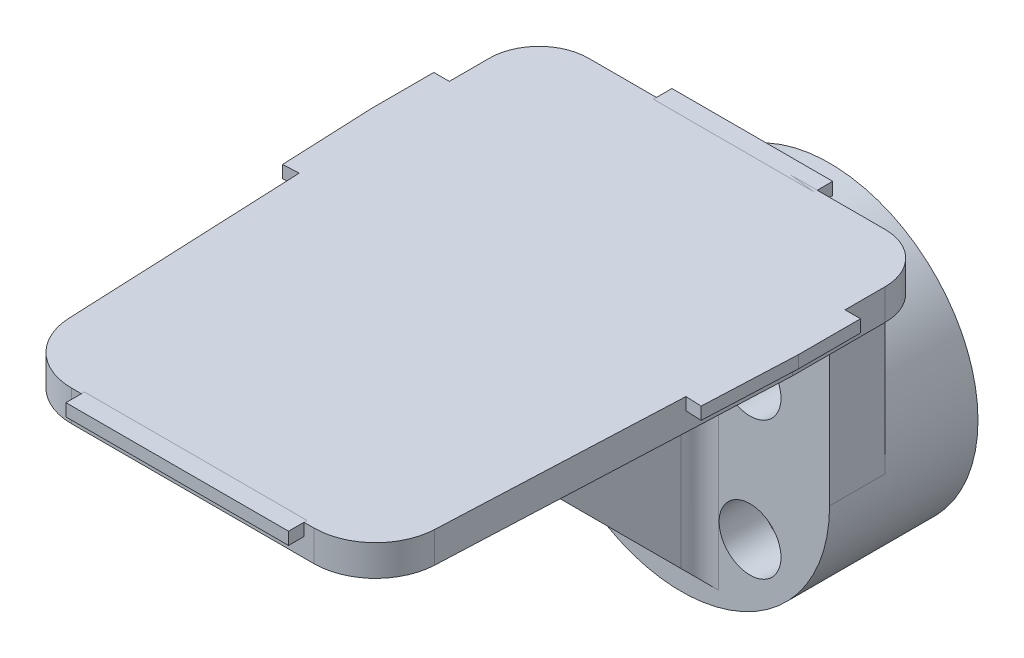
SolidWorks part; units mm, degrees
ref_plane "Front Plane" through (0, 0, 0) normal (0, 0, 1) x (1, 0, 0)
ref_plane "Top Plane" through (0, 0, 0) normal (0, 1, 0) x (1, 0, 0)
ref_plane "Right Plane" through (0, 0, 0) normal (1, 0, 0) x (0, 0, -1)
sketch "Sketch1" plane through (0, 0, 0) normal (0, 0, 1) x (1, 0, 0)
  line L0 (0, 0) -> (0, 50000) construction
  line L1 (0.349, 0) -> (50000.349, 0) construction
  line L2 (0.5678, 0.5678) -> (35355.9068, 35355.9068) construction
  line L3 (0, 0) -> (-35355.3391, 35355.3391) construction
  circle A0 centre (0, 0) radius 20.5
  circle A1 centre (0, 0) radius 24
  dimension "D1" = 41
  dimension "D2" = 48
  dimension "D3" = 45
extrude "Boss-Extrude3" add sketch "Sketch1" along normal blind 5 and the other way blind 15 contours A1 A0 | A0 region at (0, 0, 0) region at (-23.3212, 0, 0)
extrude "Boss-Extrude4" add sketch "Sketch1<5>" along normal blind 5 and the other way blind 19 contours A1 A0 region at (-23.3212, 0, 0)
sketch "Sketch1<5>" plane through (0, 0, 0) normal (0, 0, 1) x (1, 0, 0) same geometry as "Sketch1"
sketch "Sketch3" plane through (0, 0, -15) normal (0, 0, -1) x (-1, 0, 0)
  line L0 (-141421.3562, -141421.3562) -> (176776.6953, 176776.6953) construction
  circle A0 centre (0, 0) radius 15.75 construction
  circle A1 centre (11.1369, 11.1369) radius 3
  circle A2 centre (11.1369, -11.1369) radius 3
  circle A3 centre (-11.1369, -11.1369) radius 3
  circle A4 centre (-11.1369, 11.1369) radius 3
  point P16 (0, 0)
  dimension "D1" = 6
  dimension "D2" = 31.5
  dimension "D3" = 4
extrude "Cut-Extrude1" cut sketch "Sketch3" against normal through all and the other way through all
ref_plane "Plane1" through (0, 0, 34.7) normal (0, 0, 1) x (1, 0, 0)
ref_plane "Plane2" through (0, 34.2, 0) normal (0, 1, 0) x (1, 0, 0)
sketch "Sketch6" plane through (0, 34.2, 4.7) normal (0, -1, 0) x (1, 0, 0)
  line L0 (32, -0.7) -> (32, 14.3)
  line L3 (24, -8.7) -> (-24, -8.7)
  line L7 (-32, -0.7) -> (-32, 14.3)
  line L8 (32, 14.3) -> (29.5796, 69.7362)
  line L9 (19.5891, 79.3) -> (-19.5891, 79.3)
  line L10 (-29.5796, 69.7362) -> (-32, 14.3)
  arc A2 (19.5891, 79.3) -> (29.5796, 69.7362) centre (19.5891, 69.3) cw
  arc A3 (-29.5796, 69.7362) -> (-19.5891, 79.3) centre (-19.5891, 69.3) cw
  arc A4 (24, -8.7) -> (32, -0.7) centre (24, -0.7) ccw
  arc A5 (-32, -0.7) -> (-24, -8.7) centre (-24, -0.7) ccw
  point P0 (0, 35.3)
  dimension "D1" = 177.5
  dimension "D4" = 8
  dimension "D5" = 8
  dimension "D8" = 15
  dimension "D13" = 10
  dimension "D14" = 10
  dimension "D2" = 44
  dimension "D3" = 177.5
  dimension "D6" = 32
  dimension "D7" = 32
  dimension "D9" = 15
  dimension "D10" = 44
  dimension "D11" = 40
sketch "Sketch7" plane through (0, 34.2, -5.3) normal (0, -1, 0) x (1, 0, 0)
  line L0 (0, 0.35) -> (0, 10.25) construction
  line L5 (-18, 88.8) -> (-18, 91.8)
  line L6 (-18, 88.8) -> (18, 88.8)
  line L7 (-18, 91.8) -> (18, 91.8)
  line L8 (18, 88.8) -> (18, 91.8)
  line L9 (-18, 88.8) -> (18, 91.8) construction
  line L10 (-18, 91.8) -> (18, 88.8) construction
  line L12 (13, 1.8) -> (-13, 1.8)
  line L13 (13, 1.8) -> (13, -1.2)
  line L14 (13, -1.2) -> (-13, -1.2)
  line L15 (-13, 1.8) -> (-13, -1.2)
  line L16 (13, 1.8) -> (-13, -1.2) construction
  line L17 (13, -1.2) -> (-13, 1.8) construction
  line L19 (31.5, 25.8) -> (30.8457, 40.7857)
  line L21 (30.8457, 40.7857) -> (33.8429, 40.9166)
  line L22 (33.8429, 40.9166) -> (34.5, 25.8655)
  line L24 (34.5, 15.8) -> (34.5, 25.8655)
  line L25 (31.5, 15.8) -> (34.5, 15.8)
  line L30 (24, 1.3) -> (-24, 1.3) construction
  line L31 (-29.0801, 91.2253) -> (-31.5, 25.8) construction
  line L32 (-31.5, 25.8) -> (-31.5, 15.8) construction
  line L33 (31.5, 25.8) -> (31.5, 15.8)
  line L40 (-31.5, 25.8) -> (-31.5, 15.8)
  line L41 (-31.5, 15.8) -> (-34.5, 15.8)
  line L46 (-34.5, 15.8) -> (-34.5, 25.8655)
  line L47 (-31.5, 25.8) -> (-30.8457, 40.7857)
  line L48 (-30.8457, 40.7857) -> (-33.8429, 40.9166)
  line L49 (-33.8429, 40.9166) -> (-34.5, 25.8655)
  point P1 (0, 90.3)
  point P3 (0, 0.3)
  dimension "D1" = 36
  dimension "D2" = 3
  dimension "D3" = 3
  dimension "D4" = 26
  dimension "D5" = 18.5
  dimension "D6" = 18.5
  dimension "D7" = 3
  dimension "D8" = 3
  dimension "D9" = 14
  dimension "D10" = 2.5
  dimension "D11" = 177.5
  dimension "D12" = 10
  dimension "D13" = 15
  dimension "D14" = 10.0655
  dimension "D15" = 87
  dimension "D16" = 5
extrude "Boss-Extrude6" add sketch "Sketch7" along normal blind 2 separate body contours L22 L19 | L6 L8 L7 L5 | L48 | L12 L15 L14 L13 | L19 L33 L25 L24 L22 L21 | L48 L49 L46 L41 L40 L47 | L15 L12 L13 L14 | L8 L6 L5 L7 | L13 L12 L15 L14 | L7 L8 L6 L5 region at (0, 34.2, 85) region at (0, 34.2, -5) region at (32.8047, 34.2, 23.0285) region at (-32.8047, 34.2, 23.0285)
extrude "Boss-Extrude7" add sketch "Sketch6" along normal blind 5
sketch "Sketch8" plane through (0, 29.2, 0) normal (0, -1, 0) x (1, 0, 0)
  line L2 (-24, 5) -> (-24, -4)
  line L3 (-24, -4) -> (24, -4)
  line L4 (24, 5) -> (24, -4)
  line L9 (-24, 5) -> (24, 5)
  line L11 (24, -4) -> (-24, -4) construction
  point P0 (-21.3093, -4)
  point P2 (0, 0)
  point P9 (0, -4)
  dimension "D1" = 48
  dimension "D2" = 9
  dimension "D3" = 0
extrude "Boss-Extrude8" add sketch "Sketch8" along normal up to next contours L4 L3 L2 L9
sketch "Sketch9" plane through (0, 0, 0) normal (1, 0, 0) x (0, 0, -1)
  line L0 (-5, 29.2) -> (-55, 29.2)
  line L1 (-19, 29.2) -> (-74.4362, 29.2) construction
  line L2 (-55, 29.2) -> (-5, -20.8)
  line L3 (-5, 0) -> (-5, -24) construction
  line L4 (-5, -20.8) -> (-5, 29.2)
  dimension "D1" = 50
  dimension "D2" = 50
extrude "Boss-Extrude9" add sketch "Sketch9" along normal blind 3 and the other way blind 3
fillet "Fillet1" radius 3 8 edges at (24, 29.2, 0.5) (-24, 29.2, 0.5) (13.5, 29.2, 5) (-13.5, 29.2, 5) (-3, 29.2, 30) (3, 29.2, 30) (3, 4.2, 5) (-3, 4.2, 5)
sketch "Sketch10" plane through (0, 0, -15) normal (0, 0, -1) x (-1, 0, 0)
  line L0 (-18.1036, -9.6183) -> (-8.4853, 0)
  line L5 (-25.1733, -16.688) -> (-25.0651, -16.688) construction
  line L6 (-18.1036, 9.6183) -> (-8.4853, 0)
  line L7 (-9.6183, -18.1036) -> (0, -8.4853)
  line L8 (-9.6183, 18.1036) -> (0, 8.4853)
  line L9 (0, -8.4853) -> (9.6183, -18.1036)
  line L10 (8.4853, 0) -> (18.1036, 9.6183)
  line L11 (8.4853, 0) -> (18.1036, -9.6183)
  line L12 (0, 8.4853) -> (9.6183, 18.1036)
  circle A0 centre (0, 0) radius 20.5
  point P12 (0, 0)
  dimension "D1" = 41
  dimension "D2" = 6
  dimension "D3" = 6
  dimension "D4" = 6
  dimension "D5" = 6
sketch "Sketch11" plane through (0, 0, 5) normal (0, 0, 1) x (1, 0, 0)
  circle A0 centre (-11.1369, 11.1369) radius 5
  circle A1 centre (11.1369, 11.1369) radius 5
  circle A2 centre (-11.1369, -11.1369) radius 5
  circle A3 centre (11.1369, -11.1369) radius 5
extrude "Cut-Extrude3" cut sketch "Sketch11" against normal blind 7
